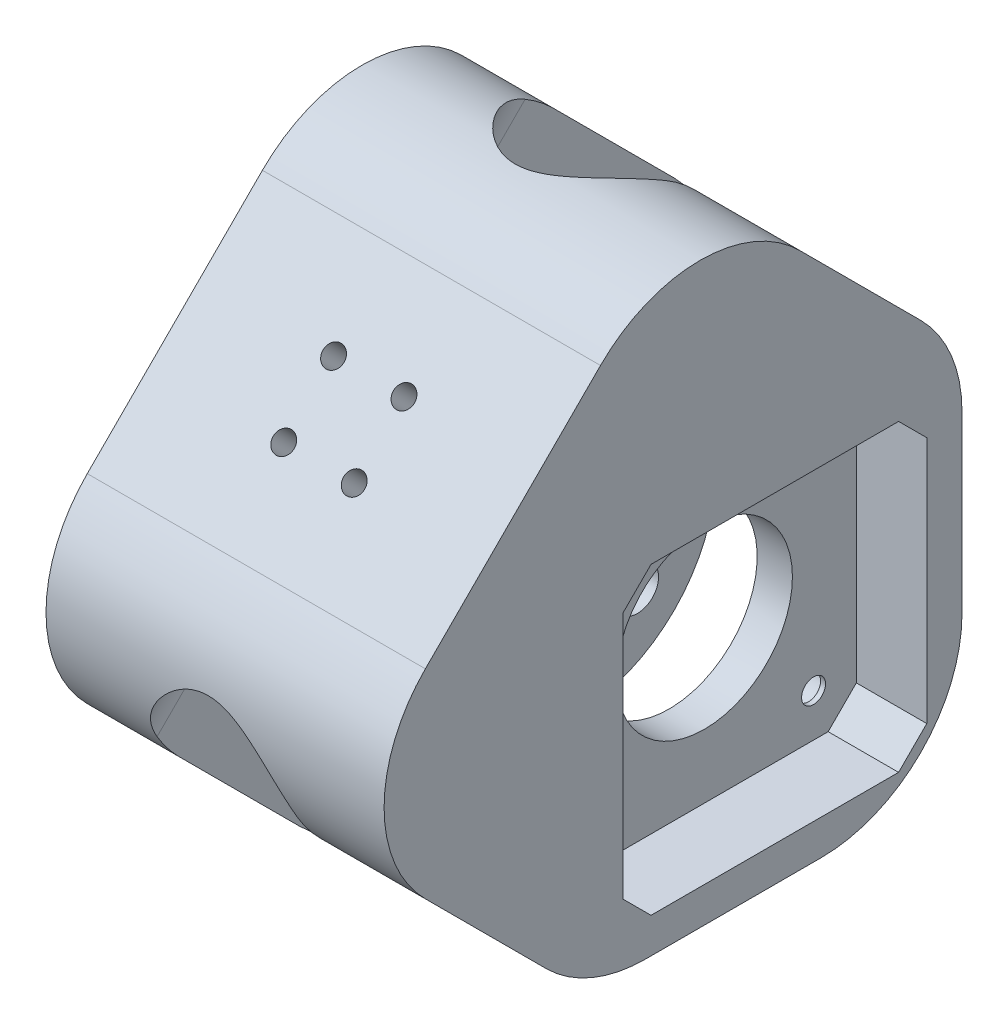
SolidWorks part; units mm, degrees
ref_plane "Front Plane" through (0, 0, 0) normal (0, 0, 1) x (1, 0, 0)
ref_plane "Top Plane" through (0, 0, 0) normal (0, 1, 0) x (1, 0, 0)
ref_plane "Right Plane" through (0, 0, 0) normal (1, 0, 0) x (0, 0, -1)
sketch "Sketch1" plane through (0, 0, 0) normal (1, 0, 0) x (0, 0, -1)
  line L0 (-11.075, 42.075) -> (42.075, 42.075) construction
  line L1 (0, 0) -> (31, 0) construction
  line L2 (0, 0) -> (0, 31) construction
  line L3 (0, 31) -> (31, 31) construction
  line L4 (31, 0) -> (31, 31) construction
  line L5 (-6.075, -6.075) -> (37.075, -6.075)
  line L6 (-6.075, -6.075) -> (-6.075, 37.075)
  line L7 (-6.075, 37.075) -> (37.075, 37.075)
  line L8 (37.075, -6.075) -> (37.075, 37.075)
  line L9 (42.075, -11.075) -> (42.075, 42.075)
  line L10 (-11.075, -11.075) -> (42.075, -11.075)
  line L11 (-11.075, -11.075) -> (-11.075, 42.075) construction
  line L12 (-11.075, -11.075) -> (-37.65, 15.5)
  line L13 (-37.65, 15.5) -> (-11.075, 42.075)
  line L14 (-11.075, 42.075) -> (15.5, 68.65)
  line L15 (15.5, 68.65) -> (42.075, 42.075)
  point P9 (31, 15.5)
  point P10 (37.075, 15.5)
  point P11 (15.5, -6.075)
  point P12 (15.5, 0)
  dimension "D2" = 31
  dimension "D3" = 43.15
  dimension "D5" = 5
extrude "Boss-Extrude1" add sketch "Sketch1" along normal blind 5 contours L5 L8 L7 L6 | L11 L10 L9 L0 L8 L5 L6 L7 region at (0, 15.5, -15.5) region at (0, -9.9475, -15.5)
extrude "Boss-Extrude2" add sketch "Sketch1<3>" along normal blind 10 from surface starting at face at (5, 20.815, -10.185)
sketch "Sketch1<3>" plane through (0, 0, 0) normal (1, 0, 0) x (0, 0, -1) same geometry as "Sketch1"
sketch "Sketch6" plane through (0, 0, 0) normal (-1, 0, 0) x (0, 0, 1)
  line L2 (11.075, -11.075) -> (-42.075, -11.075) construction
  line L3 (-42.075, -11.075) -> (-42.075, 42.075) construction
  circle A0 centre (-15.5, 15.5) radius 12.5
  point P11 (-15.5, -11.075)
  point P15 (-42.075, 15.5)
  dimension "D1" = 25
extrude "Cut-Extrude1" cut sketch "Sketch6" against normal blind 10
chamfer "Chamfer1" distance 4 angle 45 4 edges at (10, -6.075, -37.075) (10, 37.075, -37.075) (10, 37.075, 6.075) (10, -6.075, 6.075)
sketch "Sketch8" plane through (0, -11.075, 11.075) normal (0, -0.7071, 0.7071) x (1, 0, 0)
  line L0 (15, 37.5827) -> (15, 52.5827)
  line L5 (15, 37.5827) -> (0, 37.5827)
  line L6 (-33, 37.5827) -> (-20, 37.5827)
  line L7 (-33, 52.5827) -> (-33, 37.5827)
  line L8 (15, 52.5827) -> (-33, 52.5827)
  line L9 (15, 37.5827) -> (15, 0) construction
  line L10 (15, 37.5827) -> (0, 37.5827) construction
  arc A2 (0, 37.5827) -> (-20, 37.5827) centre (-10, 37.5827) ccw
  point P13 (-10, 47.5827)
  dimension "D2" = 13
  dimension "D1" = 20
  dimension "D3" = 5
extrude "Boss-Extrude10" add sketch "Sketch8" against normal up to surface (75.1655 mm away) up to face at (7.5, 55.3625, -28.7875)
extrude "Boss-Extrude11" add sketch "Sketch1<5>" along normal blind 13 from surface contours L15 L14 L13 L12 L10 L9 L8 L5 L6 L7 | L5 L8 L7 L6 region at (0, 15.5, -15.5) region at (0, -9.9475, -15.5) starting at face at (-33, 47.3783, 16.3783)
sketch "Sketch1<5>" plane through (0, 0, 0) normal (1, 0, 0) x (0, 0, -1) same geometry as "Sketch1"
fillet "Fillet1" radius 20 8 edges at (-26.5, -11.075, -42.075) (7.5, -11.075, -42.075) (-26.5, -11.075, 11.075) (7.5, -11.075, 11.075) (-26.5, 42.075, -42.075) (7.5, 42.075, -42.075) (-9, 26.1066, 48.2566) (-9, 79.2566, -4.8934)
hole_wizard "Ø3.0mm Dowel Hole1" positions "Sketch9" profile "Sketch10" hole size "Ø3.0" standard "ANSI Metric" end condition through all
sketch "Sketch9" plane through (0, 37.1816, 37.1816) normal (0, 0.7071, 0.7071) x (1, 0, 0)
  line L1 (-4, 16.9203) -> (-14, 16.9203) construction
  line L2 (-4, 16.9203) -> (-4, 26.9203) construction
  line L3 (-4, 26.9203) -> (-14, 26.9203) construction
  line L4 (-14, 16.9203) -> (-14, 26.9203) construction
  line L5 (-33, 4.3376) -> (15, 4.3376) construction
  line L6 (15, 39.503) -> (-33, 39.503) construction
  line L7 (-9, 4.3376) -> (-9, 39.503) construction
  line L9 (15, 21.9203) -> (-33, 21.9203) construction
  line L10 (15, 39.503) -> (15, 4.3376) construction
  line L11 (-33, 39.503) -> (-33, 4.3376) construction
  point P0 (-14, 16.9203)
  point P2 (-4, 16.9203)
  point P4 (-4, 26.9203)
  point P6 (-14, 26.9203)
  point P59 (-9, 16.9203)
  point P61 (-4, 21.9203)
  dimension "D1" = 10
sketch "Sketch10" plane through (-14, 49.1461, 25.2171) normal (1, 0, 0) x (0, -0.7071, 0.7071)
  line L0 (0, 0) -> (0, 90.1655)
  line L1 (0, 90.1655) -> (1.5, 90.1655)
  line L2 (1.5, 90.1655) -> (1.5, 0)
  line L5 (1.5, 0) -> (0, 0)
  line L11 (0, -6.35) -> (0, 107.95) construction
  dimension "Thru Hole Dia." = 3
  dimension "Thru Hole Depth" = 90.1655
sketch "Sketch11" plane through (-20, 0, 0) normal (1, 0, 0) x (0, 0, -1)
  circle A0 centre (15.5, 15.5) radius 11
  circle A1 centre (15.5, 15.5) radius 12.5 construction
  circle A2 centre (15.5, 15.5) radius 4.5
  point P5 (0, 0)
  dimension "D1" = 22
  dimension "D2" = 9
extrude "Cut-Extrude2" cut sketch "Sketch11" against normal blind 7
extrude "Cut-Extrude3" cut sketch "Sketch11<2>" against normal through all contours A2 region at (-20, 15.5, -15.5)
sketch "Sketch11<2>" plane through (-20, 0, 0) normal (1, 0, 0) x (0, 0, -1) same geometry as "Sketch11"
hole_wizard "CBORE for M3 Hex Head Machine Screw2" positions "Sketch4" profile "Sketch5" counterbore size "M3" standard "ANSI Metric" end condition through all
sketch "Sketch4" plane through (0, 0, 0) normal (-1, 0, 0) x (0, 0, 1)
  line L1 (0, 0) -> (-31, 0) construction
  line L2 (0, 0) -> (0, 31) construction
  line L3 (0, 31) -> (-31, 31) construction
  line L4 (-31, 0) -> (-31, 31) construction
  point P0 (-31, 31)
  point P2 (0, 0)
  point P5 (0, 31)
  point P7 (-31, 0)
  dimension "D1" = 31
sketch "Sketch5" plane through (0, 31, -31) normal (0, 1, 0) x (0, 0, 1)
  line L0 (0, 0) -> (0, 15)
  line L1 (0, 15) -> (1.7, 15)
  line L3 (1.7, 15) -> (1.7, 4.3)
  line L4 (1.7, 4.3) -> (3, 4.3)
  line L5 (3, 4.3) -> (3, 0)
  line L7 (3, 0) -> (0, 0)
  line L11 (0, -6.35) -> (0, 107.95) construction
  dimension "Thru Hole Dia." = 3.4
  dimension "Thru Hole Depth" = 15
  dimension "C'Bore Dia." = 6
  dimension "C'Bore Depth" = 4.3
sketch "Sketch13" plane through (-33, 0, 0) normal (-1, 0, 0) x (0, 0, 1)
  circle A0 centre (0, 31) radius 3
  circle A1 centre (0, 0) radius 3
  circle A2 centre (-31, 0) radius 3
  circle A3 centre (-31, 31) radius 3
  dimension "D1" = 6
extrude "Cut-Extrude4" cut sketch "Sketch13" against normal up to surface (13 mm away) up to face at (-20, 15.5, -26.5)
